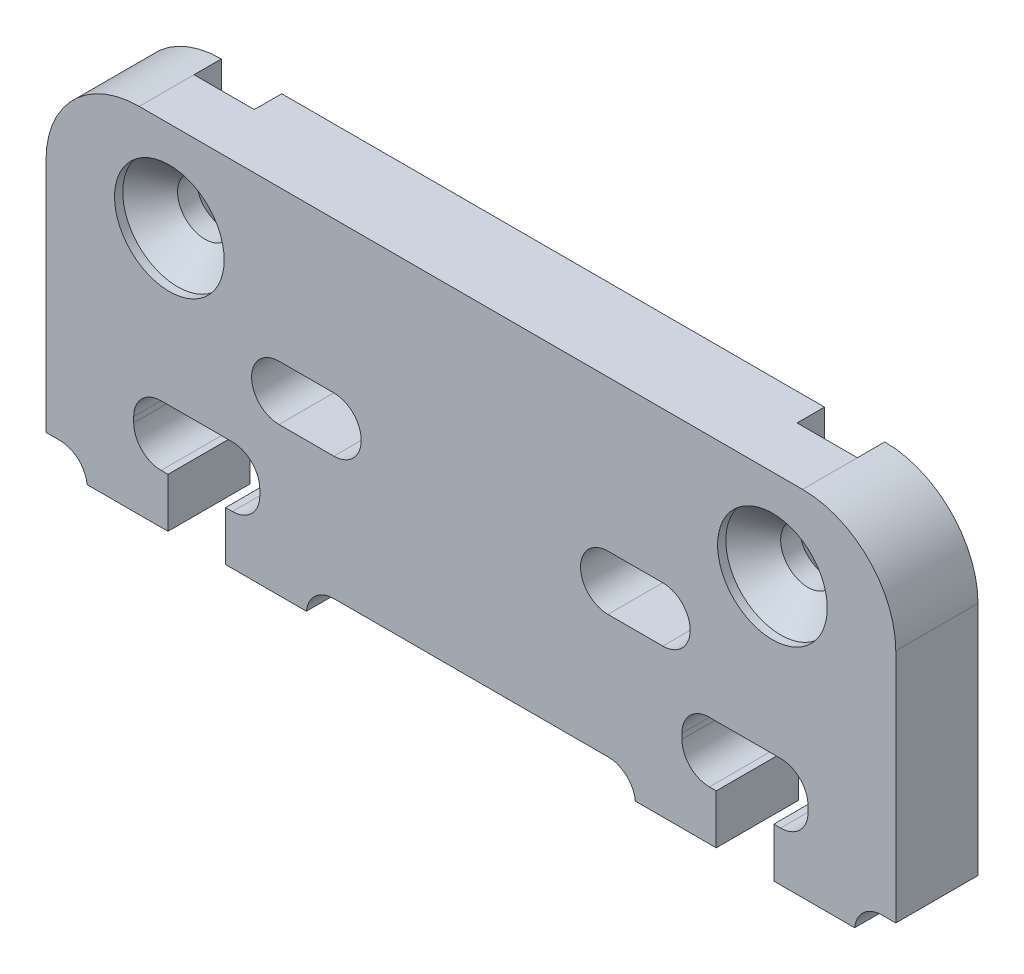
SolidWorks part; units mm, degrees
ref_plane "Front Plane" through (0, 0, 0) normal (0, 0, 1) x (1, 0, 0)
ref_plane "Top Plane" through (0, 0, 0) normal (0, 1, 0) x (1, 0, 0)
ref_plane "Right Plane" through (0, 0, 0) normal (1, 0, 0) x (0, 0, -1)
sketch "Sketch1" plane through (0, 0, 0) normal (0, 0, 1) x (1, 0, 0)
  line L0 (-10, -6.9) -> (-10, 6) construction
  line L1 (-15.5, 6) -> (15.5, 6)
  line L2 (-15.5, 6) -> (-15.5, -6)
  line L3 (-15.5, -6) -> (15.5, -6)
  line L4 (15.5, 6) -> (15.5, -6)
  line L5 (-15.5, 6) -> (15.5, -6) construction
  line L6 (-15.5, -6) -> (15.5, 6) construction
  line L7 (-15.5, -6) -> (-6, -6)
  line L9 (-14, -6.9) -> (-6, -6.9)
  line L10 (-6, -6) -> (-6, -6.9)
  line L11 (0, 6) -> (0, -6) construction
  line L12 (-11.05, -5.1) -> (-8.95, -5.1)
  line L13 (-11.05, -5.1) -> (-11.05, -6.9)
  line L14 (-11.05, -6.9) -> (-8.95, -6.9)
  line L15 (-8.95, -5.1) -> (-8.95, -6.9)
  line L16 (-11.05, -5.1) -> (-8.95, -6.9) construction
  line L17 (-11.05, -6.9) -> (-8.95, -5.1) construction
  line L18 (-12.3, -2.9) -> (-7.7, -2.9)
  line L19 (-12.3, -2.9) -> (-12.3, -5.1)
  line L20 (-12.3, -5.1) -> (-7.7, -5.1)
  line L21 (-7.7, -2.9) -> (-7.7, -5.1)
  line L22 (-12.3, -2.9) -> (-7.7, -5.1) construction
  line L23 (-12.3, -5.1) -> (-7.7, -2.9) construction
  line L24 (12.3, -2.9) -> (7.7, -2.9)
  line L25 (12.3, -2.9) -> (12.3, -5.1)
  line L26 (12.3, -5.1) -> (7.7, -5.1)
  line L27 (7.7, -2.9) -> (7.7, -5.1)
  line L28 (11.05, -5.1) -> (8.95, -5.1)
  line L29 (11.05, -5.1) -> (11.05, -6.9)
  line L30 (11.05, -6.9) -> (8.95, -6.9)
  line L31 (8.95, -5.1) -> (8.95, -6.9)
  line L32 (15.5, -6) -> (6, -6)
  line L33 (6, -6) -> (6, -6.9)
  line L34 (14, -6.9) -> (6, -6.9)
  line L36 (-14, -6.9) -> (-14, -6)
  line L37 (14, -6.9) -> (14, -6)
  line L38 (10, -2.9) -> (10, -6.9) construction
  line L39 (7, -0.5) -> (5, -0.5) construction
  line L40 (7, -1.5) -> (5, -1.5)
  line L41 (7, 0.5) -> (5, 0.5)
  line L42 (-7, -0.5) -> (-5, -0.5) construction
  line L43 (-7, -1.5) -> (-5, -1.5)
  line L44 (-7, 0.5) -> (-5, 0.5)
  arc A0 (7, -1.5) -> (7, 0.5) centre (7, -0.5) ccw
  arc A1 (5, 0.5) -> (5, -1.5) centre (5, -0.5) ccw
  arc A2 (-7, -1.5) -> (-7, 0.5) centre (-7, -0.5) cw
  arc A3 (-5, 0.5) -> (-5, -1.5) centre (-5, -0.5) cw
  point P0 (0, 0)
  point P11 (-10, -6)
  point P16 (-10, -4)
  point P40 (6, -0.5)
  point P47 (-6, -0.5)
  dimension "D1" = 31
  dimension "D2" = 12
  dimension "D3" = 0.9
  dimension "D4" = 8
  dimension "D5" = 2.1
  dimension "D6" = 1.8
  dimension "D7" = 2.2
  dimension "D8" = 4.6
  dimension "D9" = 20
  dimension "D10" = 2
  dimension "D11" = 2
  dimension "D12" = 12
  dimension "D13" = 5.5
extrude "Base shape" add sketch "Sketch1" along normal blind 3 contours L31 L26 L27 L24 L25 L29 L3 L4 L1 L2 L13 L20 L19 L18 L21 L15 | L3 L15 L9 L10 | L13 L3 L9 | L34 L31 L3 L33 | L3 L29 L34 region at (0, 0.3269, 0) region at (-12.525, -6.45, 0) region at (12.525, -6.45, 0) region at (-7.475, -6.45, 0) region at (7.475, -6.45, 0)
fillet "Edge radiuses" radius 3.4 2 edges at (15.5, 6, 1.5) (-15.5, 6, 1.5)
sketch "Sketch2" plane through (0, 0, 0) normal (0, 0, -1) x (-1, 0, 0)
  line L0 (0, 6) -> (0, -6) construction
  line L10 (12.1, 6) -> (-12.1, 6) construction
  line L11 (6, -6) -> (-6, -6) construction
  line L16 (-14, -6) -> (-15.5, -6) construction
  line L17 (-12.1, 6.1) -> (-9.9, 6.1)
  line L18 (-12.1, 6.1) -> (-12.1, -0.2)
  line L19 (-11.6, -0.7) -> (-10.4, -0.7)
  line L20 (-9.9, 6.1) -> (-9.9, -0.2)
  line L21 (-12.1, 6.1) -> (-9.9, -0.7) construction
  line L22 (-12.1, -0.7) -> (-9.9, 6.1) construction
  line L23 (12.1, 6.1) -> (9.9, 6.1)
  line L24 (12.1, 6.1) -> (12.1, -0.2)
  line L25 (11.6, -0.7) -> (10.4, -0.7)
  line L26 (9.9, 6.1) -> (9.9, -0.2)
  arc A8 (-10.4, -0.7) -> (-9.9, -0.2) centre (-10.4, -0.2) ccw
  arc A9 (-12.1, -0.2) -> (-11.6, -0.7) centre (-11.6, -0.2) ccw
  arc A10 (12.1, -0.2) -> (11.6, -0.7) centre (11.6, -0.2) cw
  arc A11 (10.4, -0.7) -> (9.9, -0.2) centre (10.4, -0.2) cw
  point P6 (-11, 2.7)
  dimension "D5" = 0.5
  dimension "D1" = 6.8
  dimension "D2" = 2.2
  dimension "D3" = 22
  dimension "D4" = 8.7
extrude "Camera mount pockets" cut sketch "Sketch2" against normal blind 1
sketch "Sketch3" plane through (0, 0, 1) normal (0, 0, -1) x (-1, 0, 0)
  line L3 (0, 6) -> (0, -6) construction
  line L5 (6, -6) -> (-6, -6) construction
  line L6 (-11.6, -0.7) -> (-10.4, -0.7) construction
  line L7 (-12.1, 6.1) -> (-9.9, 6.1)
  line L8 (-12.1, 6.1) -> (-12.1, -0.7)
  line L9 (-12.1, -0.7) -> (-9.9, -0.7)
  line L10 (-9.9, 6.1) -> (-9.9, -0.7)
  line L11 (-12.1, 6.1) -> (-9.9, -0.7) construction
  line L12 (-12.1, -0.7) -> (-9.9, 6.1) construction
  line L13 (-12.1, 6) -> (-12.1, -0.2) construction
  circle A0 centre (-11, 2.7) radius 1
  circle A1 centre (11, 2.7) radius 1
  point P2 (-11, 2.7)
  point P17 (-11, -0.7)
  point P18 (-11, -0.7)
  dimension "D1" = 2
  dimension "D2" = 6.8
extrude "Camera mount holes" cut sketch "Sketch3" against normal up to next contours A0 | A1 region at (11, 2.7, 1) region at (-11, 2.7, 1)
hole_wizard "CSK for M2 Flat Head Machine Screw1" positions "Sketch4" profile "Sketch5" countersink size "M2" standard "ANSI Metric" end condition through all
sketch "Sketch4" plane through (0, 0, 3) normal (0, 0, 1) x (1, 0, 0)
  point P0 (-11, 2.7)
  point P3 (11, 2.7)
sketch "Sketch5" plane through (-11, 2.7, 3) normal (1, 0, 0) x (0, -1, 0)
  line L0 (0, 0) -> (0, 3)
  line L1 (0, 3) -> (1, 3)
  line L2 (1, 3) -> (1, 1.3)
  line L3 (1, 1.3) -> (2, 0.3)
  line L4 (2, 0.3) -> (2, 0)
  line L6 (2, 0) -> (0, 0)
  line L7 (-1, 1.3) -> (-2, 0.3) construction
  line L11 (0, -6.35) -> (0, 107.95) construction
  dimension "Thru Hole Dia." = 2
  dimension "Thru Hole Depth" = 3
  dimension "C'Sink Dia." = 4
  dimension "C'Sink Angle" = 90
  dimension "Head Clearance" = 0.3
fillet "1mm milling radiuses" radius 1 12 edges at (-7.7, -2.9, 1.5) (-7.7, -5.1, 1.5) (12.3, -5.1, 1.5) (12.3, -2.9, 1.5) (7.7, -2.9, 1.5) (7.7, -5.1, 1.5) (-12.3, -5.1, 1.5) (-12.3, -2.9, 1.5) (14, -6, 1.5) (6, -6, 1.5) (-14, -6, 1.5) (-6, -6, 1.5)
sketch "Slot sketch" plane through (0, 0, 1) normal (0, 0, -1) x (-1, 0, 0)
  line L0 (0, 6) -> (0, -6) construction
  line L3 (-12.1, 7.2) -> (-9.9, 7.2)
  line L4 (-12.1, 6) -> (-12.1, -0.2)
  line L5 (-11.6, -0.7) -> (-10.4, -0.7)
  line L6 (-9.9, -0.2) -> (-9.9, 6)
  line L7 (-9.9, 6) -> (-12.1, 6)
  line L9 (-11.6, -0.7) -> (-10.4, -0.7)
  line L12 (9.9, 6) -> (-9.9, 6) construction
  line L25 (-12.1, -0.2) -> (-12.1, 7.2)
  line L26 (-9.9, -0.2) -> (-9.9, 7.2)
  line L27 (11.6, -0.7) -> (10.4, -0.7)
  line L28 (12.1, -0.2) -> (12.1, 7.2)
  line L29 (12.1, 7.2) -> (9.9, 7.2)
  line L30 (9.9, -0.2) -> (9.9, 7.2)
  line L31 (5.005, -6) -> (-5.005, -6) construction
  arc A2 (-12.1, -0.2) -> (-11.6, -0.7) centre (-11.6, -0.2) ccw
  arc A3 (-10.4, -0.7) -> (-9.9, -0.2) centre (-10.4, -0.2) ccw
  arc A4 (-12.1, -0.2) -> (-11.6, -0.7) centre (-11.6, -0.2) ccw
  arc A5 (-10.4, -0.7) -> (-9.9, -0.2) centre (-10.4, -0.2) ccw
  arc A6 (10.4, -0.7) -> (9.9, -0.2) centre (10.4, -0.2) cw
  arc A7 (12.1, -0.2) -> (11.6, -0.7) centre (11.6, -0.2) cw
  dimension "D3" = 1.2
  dimension "D1" = 0
sketch "Sketch8" plane through (0, 0, 0) normal (0, 0, -1) x (-1, 0, 0)
  line L0 (-14, -6) -> (14, -6) construction
  line L1 (-14, -6) -> (-2, 6) construction
  line L2 (9.9, 6) -> (-9.9, 6) construction
  line L3 (0, 6) -> (0, -6) construction
  line L4 (-11.05, -6.9) -> (-8.95, -6.9) construction
  line L5 (-10, -6.9) -> (-10, -2.9) construction
  line L6 (-11.3, -2.9) -> (-8.7, -2.9) construction
  line L7 (-15.5, -6) -> (-14, -6) construction
  line L8 (-14, -6) -> (-14, -6.9) construction
  circle A0 centre (-14.7071, -6.7071) radius 1
  circle A1 centre (14.7071, -6.7071) radius 1
  circle A2 centre (-5.2929, -6.7071) radius 1
  circle A3 centre (5.2929, -6.7071) radius 1
  dimension "D2" = 2
  dimension "D1" = 45
extrude "Square cuts" [suppressed] cut sketch "Sketch8" against normal up to next
